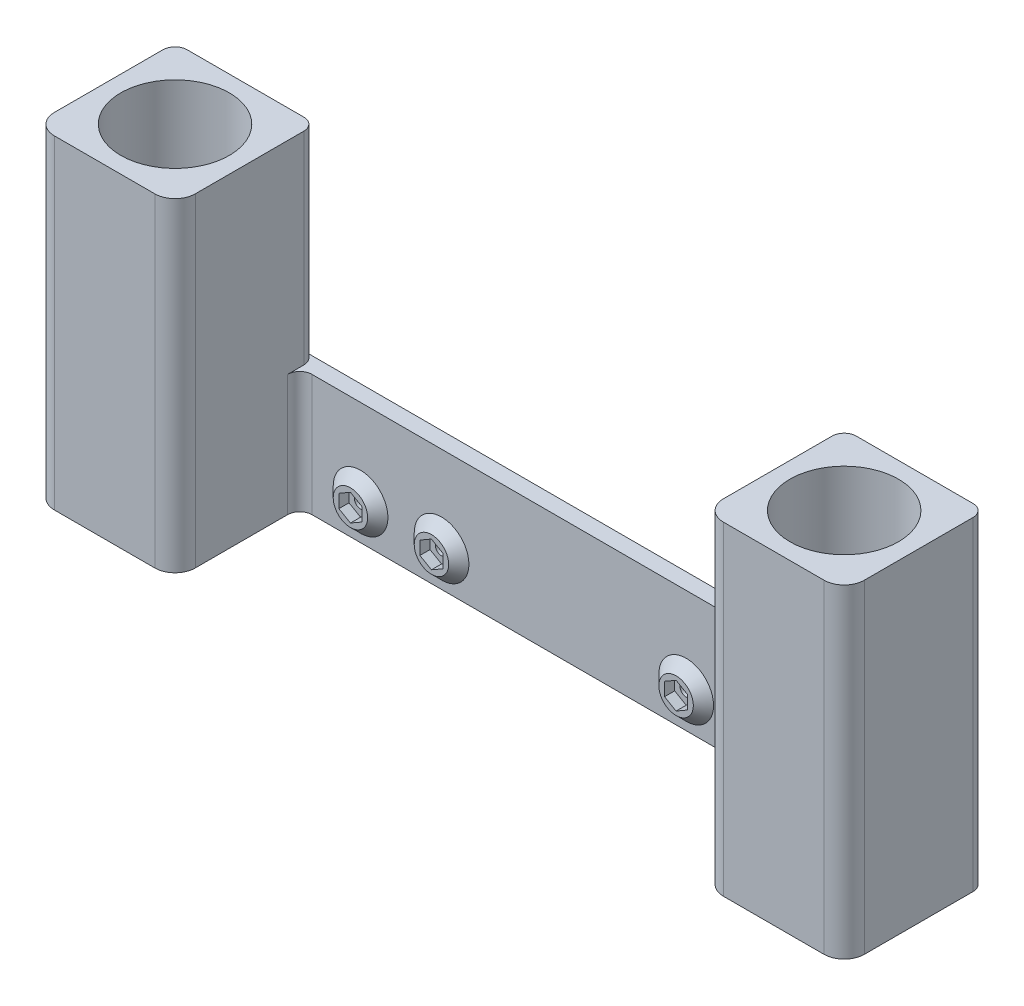
SolidWorks part; units mm, degrees
ref_plane "Front Plane" through (0, 0, 0) normal (0, 0, 1) x (1, 0, 0)
ref_plane "Top Plane" through (0, 0, 0) normal (0, 1, 0) x (1, 0, 0)
ref_plane "Right Plane" through (0, 0, 0) normal (1, 0, 0) x (0, 0, -1)
sketch "Sketch1" plane through (0, 0, 0) normal (0, 1, 0) x (1, 0, 0)
  line L1 (-17.4, 17.4) -> (17.4, 17.4)
  line L2 (-17.4, 17.4) -> (-17.4, -17.4)
  line L3 (-17.4, -17.4) -> (17.4, -17.4)
  line L4 (17.4, 13.4) -> (17.4, -17.4)
  line L5 (-17.4, 17.4) -> (17.4, -17.4) construction
  line L6 (-17.4, -17.4) -> (17.4, 17.4) construction
  line L11 (17.4, 17.4) -> (82.6, 17.4)
  line L13 (17.4, 13.4) -> (82.6, 13.4)
  line L14 (82.6, 17.4) -> (82.6, 13.4)
  circle A0 centre (0, 0) radius 13.4
  dimension "D1" = 26.8
  dimension "D2" = 34.8
  dimension "D3" = 34.8
extrude "Boss-Extrude1" add sketch "Sketch1" along normal blind 30 contours L14 L11 L4 L13 | L4 L1 L2 L3 A0 region at (14.3654, 0, -4.4245)
sketch "Sketch4" plane through (0, 0, -13.4) normal (0, 0, 1) x (1, 0, 0)
  line L1 (17.4, 30) -> (17.4, 0) construction
  line L2 (17.4, 0) -> (82.6, 0) construction
  circle A0 centre (32.4, 8.75) radius 1.55
  circle A1 centre (52.4, 8.75) radius 1.55
  dimension "D1" = 8.75
  dimension "D2" = 3.1
  dimension "D3" = 15
  dimension "D4" = 20
extrude "Cut-Extrude1" cut sketch "Sketch4" against normal up to next
sketch "Sketch5" plane through (0, 0, -13.4) normal (0, 0, 1) x (1, 0, 0)
  line L1 (32.4, 12.0409) -> (29.55, 10.3954)
  line L2 (29.55, 10.3954) -> (29.55, 7.1046)
  line L3 (29.55, 7.1046) -> (32.4, 5.4591)
  line L4 (32.4, 5.4591) -> (35.25, 7.1046)
  line L5 (35.25, 7.1046) -> (35.25, 10.3954)
  line L6 (35.25, 10.3954) -> (32.4, 12.0409)
  line L7 (52.4, 12.0409) -> (49.55, 10.3954)
  line L8 (49.55, 10.3954) -> (49.55, 7.1046)
  line L9 (49.55, 7.1046) -> (52.4, 5.4591)
  line L10 (52.4, 5.4591) -> (55.25, 7.1046)
  line L11 (55.25, 7.1046) -> (55.25, 10.3954)
  line L12 (55.25, 10.3954) -> (52.4, 12.0409)
  circle A0 centre (32.4, 8.75) radius 2.85 construction
  circle A1 centre (32.4, 8.75) radius 4.25
  circle A2 centre (52.4, 8.75) radius 2.85 construction
  circle A3 centre (52.4, 8.75) radius 4.25
  point P1 (35.25, 8.75)
  dimension "D2" = 8.5
  dimension "D1" = 5.7
extrude "Boss-Extrude4" add sketch "Sketch5" along normal blind 2.5
chamfer "Chamfer1" distance 2.5 angle 45 2 edges at (48.15, 8.75, -13.4) (28.15, 8.75, -13.4)
sketch "Sketch6" plane through (0, 30, 0) normal (0, 1, 0) x (1, 0, 0)
  line L1 (17.4, -17.4) -> (-17.4, -17.4)
  line L2 (17.4, -17.4) -> (17.4, 17.4)
  line L3 (17.4, 17.4) -> (-17.4, 17.4)
  line L4 (-17.4, -17.4) -> (-17.4, 17.4)
  circle A1 centre (0, 0) radius 13.4 construction
  circle A2 centre (0, 0) radius 13.4
extrude "Boss-Extrude5" add sketch "Sketch6" along normal blind 50
mirror "Mirror1" about plane through (82.6, 30, 0) normal (1, 0, 0) of "Cut-Extrude1", "Chamfer1", "Boss-Extrude4", "Boss-Extrude1", "Boss-Extrude5"
fillet "Fillet1" radius 5 4 edges at (182.6, 40, 17.4) (147.8, 40, 17.4) (17.4, 40, 17.4) (-17.4, 40, 17.4)
fillet "Fillet2" radius 3 6 edges at (17.4, 15, -13.4) (147.8, 15, -13.4) (182.6, 40, -17.4) (-17.4, 40, -17.4) (147.8, 55, -17.4) (17.4, 55, -17.4)
